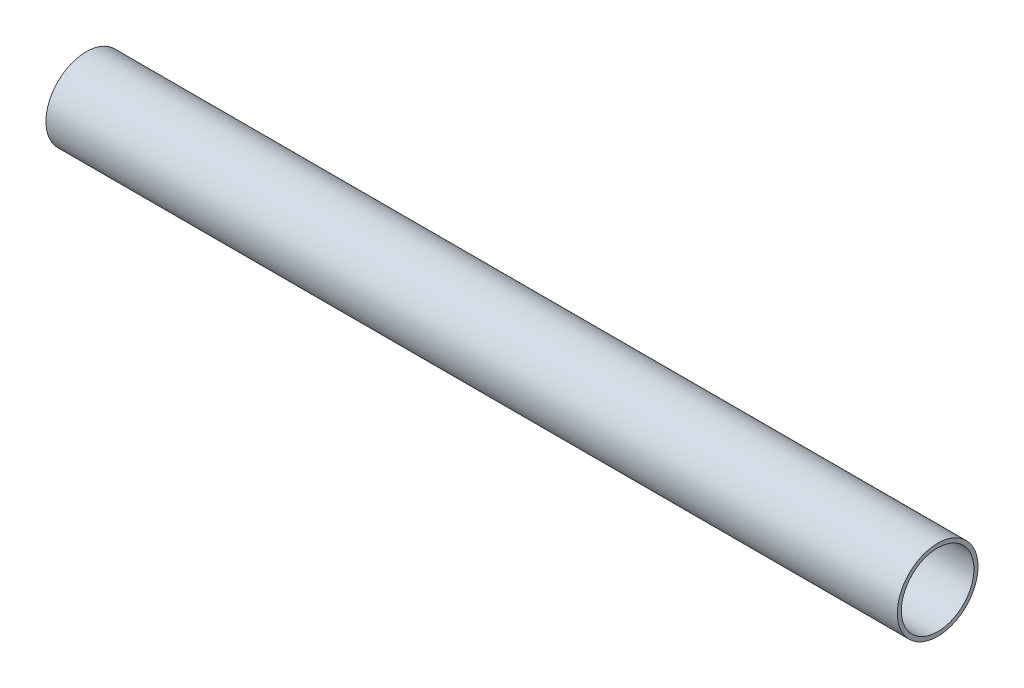
SolidWorks part; units mm, degrees
material "PC High Viscosity"
ref_plane "Front Plane" through (0, 0, 0) normal (0, 0, 1) x (1, 0, 0)
ref_plane "Top Plane" through (0, 0, 0) normal (0, 1, 0) x (1, 0, 0)
ref_plane "Right Plane" through (0, 0, 0) normal (1, 0, 0) x (0, 0, -1)
sketch "Sketch1" plane through (0, 0, 0) normal (1, 0, 0) x (0, 0, -1)
  circle A0 centre (0, 0) radius 15.875
  dimension "D1" = 31.75
extrude "Extrude-Thin1" add sketch "Sketch1" along normal mid plane 334.9625 thin thin type one direction reverse wall 1.5875
sketch "Sketch2" plane through (0, 0, 0) normal (0, 0, 1) x (1, 0, 0)
  line L0 (-167.4812, -15.875) -> (167.4812, -15.875) construction
  line L1 (105.2063, -15.875) -> (126.2062, -15.875)
  line L2 (105.2063, -15.875) -> (105.2063, 15.875)
  line L3 (105.2063, 15.875) -> (126.2062, 15.875)
  line L4 (126.2062, -15.875) -> (126.2062, 15.875)
  line L5 (167.4812, 15.875) -> (-167.4812, 15.875) construction
  line L6 (167.4812, -15.875) -> (167.4812, 15.875) construction
  line L7 (0, 0) -> (0, 11.1276) construction
  line L8 (-126.2062, -15.875) -> (-126.2062, 15.875)
  line L9 (-105.2063, 15.875) -> (-126.2062, 15.875)
  line L10 (-105.2063, -15.875) -> (-105.2063, 15.875)
  line L11 (-105.2063, -15.875) -> (-126.2062, -15.875)
  line L13 (167.4812, -15.875) -> (165.1572, -15.875)
  line L14 (167.4812, -15.875) -> (167.4812, 15.875)
  line L15 (167.4812, 15.875) -> (165.1572, 15.875)
  line L16 (165.1572, -15.875) -> (165.1572, 15.875)
  dimension "D1" = 41.275
  dimension "D2" = 21
  dimension "D3" = 2.3241
equation "\"D2@Sketch2\"=21mm"
